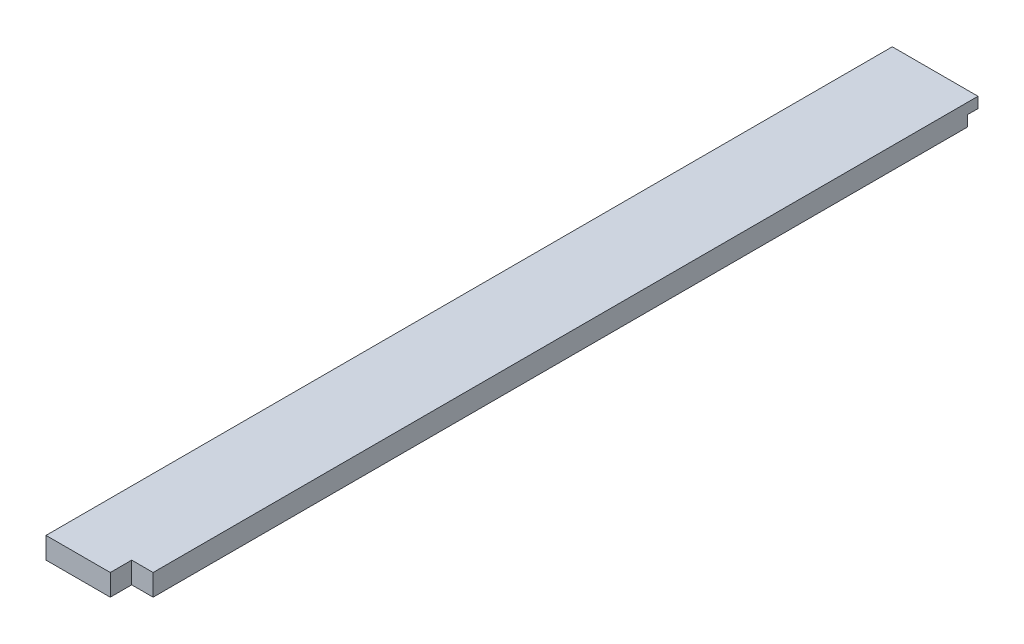
SolidWorks part; units mm, degrees
ref_plane "Front Plane" through (0, 0, 0) normal (0, 0, 1) x (1, 0, 0)
ref_plane "Top Plane" through (0, 0, 0) normal (0, 1, 0) x (1, 0, 0)
ref_plane "Right Plane" through (0, 0, 0) normal (1, 0, 0) x (0, 0, -1)
sketch "Sketch1" plane through (0, 0, 0) normal (0, 0, 1) x (1, 0, 0)
  line L0 (0, 12.7) -> (38.1, 12.7)
  line L3 (50.8, 6.35) -> (50.8, 0)
  line L4 (50.8, 0) -> (0, 0)
  line L5 (0, 0) -> (0, 12.7)
  line L6 (50.8, 6.35) -> (50.8, 12.7)
  line L7 (50.8, 12.7) -> (38.1, 12.7)
  dimension "D2" = 6.35
  dimension "D3" = 50.8
extrude "Boss-Extrude1" add sketch "Sketch1" along normal blind 501.65
sketch "Sketch3" plane through (0, 0, 0) normal (0, 1, 0) x (1, 0, 0)
  line L5 (0, -501.65) -> (0, 0) construction
  line L6 (0, -6.35) -> (50.8, -6.35)
  line L7 (0, -6.35) -> (0, 0)
  line L8 (0, 0) -> (50.8, 0)
  line L9 (50.8, -6.35) -> (50.8, 0)
  dimension "D1" = 6.35
extrude "Cut-Extrude1" cut sketch "Sketch3" along normal blind 6.35
sketch "Sketch4" plane through (0, 0, 0) normal (0, -1, 0) x (1, 0, 0)
  line L1 (50.8, 501.65) -> (38.1, 501.65)
  line L2 (50.8, 501.65) -> (50.8, 488.95)
  line L3 (50.8, 488.95) -> (38.1, 488.95)
  line L4 (38.1, 501.65) -> (38.1, 488.95)
  dimension "D1" = 12.7
  dimension "D2" = 12.7
extrude "Cut-Extrude4" cut sketch "Sketch4" against normal through all
